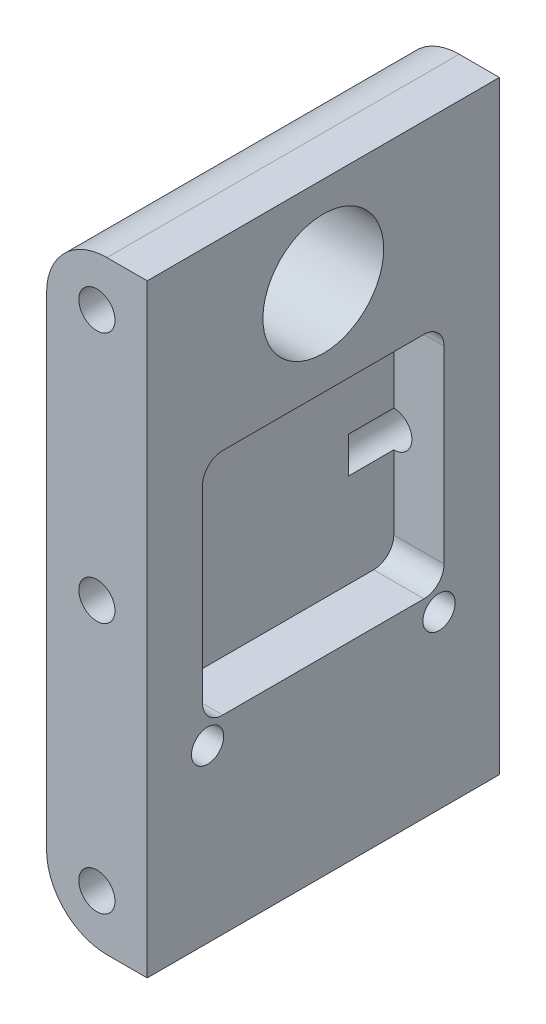
SolidWorks part; units mm, degrees
ref_plane "Front Plane" through (0, 0, 0) normal (0, 0, 1) x (1, 0, 0)
ref_plane "Top Plane" through (0, 0, 0) normal (0, 1, 0) x (1, 0, 0)
ref_plane "Right Plane" through (0, 0, 0) normal (1, 0, 0) x (0, 0, -1)
sketch "Sketch1" plane through (0, 0, 0) normal (1, 0, 0) x (0, 0, -1)
  line L0 (17.5, 60) -> (17.5, 0) construction
  line L1 (0, 0) -> (35, 0)
  line L2 (0, 0) -> (0, 60)
  line L3 (0, 60) -> (35, 60)
  line L11 (35, 60) -> (35, 0)
  circle A0 centre (17.5, 51) radius 6
  circle A4 centre (6, 17) radius 1.6
  circle A5 centre (29, 17) radius 1.6
  point P9 (0, 0)
  point P10 (0, 0)
  point P11 (0, 0)
  point P12 (0, 0)
  point P13 (0, 0)
  point P22 (17.5, 12)
  point P27 (17.5, 12)
  dimension "D1" = 35
  dimension "D2" = 60
extrude "Boss-Extrude1" add sketch "Sketch1" along normal blind 10
sketch "Sketch2" plane through (0, 0, -35) normal (0, 0, -1) x (-1, 0, 0)
  circle A0 centre (-5, 55) radius 1.8
  circle A1 centre (-5, 30) radius 1.8
  circle A2 centre (-5, 5) radius 1.8
  dimension "D1" = 3
extrude "Cut-Extrude1" cut sketch "Sketch2" against normal blind 10
sketch "Sketch3" plane through (0, 0, 0) normal (0, 0, 1) x (1, 0, 0)
  circle A0 centre (5, 55) radius 1.8
  circle A1 centre (5, 30) radius 1.8
  circle A2 centre (5, 5) radius 1.8
  dimension "D1" = 3
extrude "Cut-Extrude2" cut sketch "Sketch3" against normal blind 10
sketch "Sketch4" plane through (10, 0, 0) normal (1, 0, 0) x (0, 0, -1)
  line L0 (17.5, 60) -> (17.5, 0) construction
  line L1 (35, 60) -> (0, 60) construction
  line L2 (0, 0) -> (35, 0) construction
  line L4 (29.5, 31.881) -> (29.5, 20.881)
  line L5 (5.5, 31.881) -> (5.5, 20.881)
  line L6 (7.5, 18.881) -> (27.5, 18.881)
  line L8 (29.5, 36.6402) -> (29.5, 31.881)
  line L10 (5.5, 36.6402) -> (5.5, 31.881)
  line L11 (5.5, 36.6402) -> (5.5, 39.6402)
  line L12 (7.5, 41.6402) -> (27.5, 41.6402)
  line L13 (29.5, 39.6402) -> (29.5, 36.6402)
  arc A0 (5.5, 20.881) -> (7.5, 18.881) centre (7.5, 20.881) ccw
  arc A1 (29.5, 20.881) -> (27.5, 18.881) centre (27.5, 20.881) cw
  arc A6 (27.5, 41.6402) -> (29.5, 39.6402) centre (27.5, 39.6402) cw
  arc A7 (5.5, 39.6402) -> (7.5, 41.6402) centre (7.5, 39.6402) cw
  point P9 (17.5, 33.881)
  dimension "D1" = 2
  dimension "D2" = 2
extrude "Cut-Extrude3" cut sketch "Sketch4" against normal blind 5
fillet "Fillet1" radius 6 2 edges at (0, 60, -17.5) (0, 0, -17.5)
